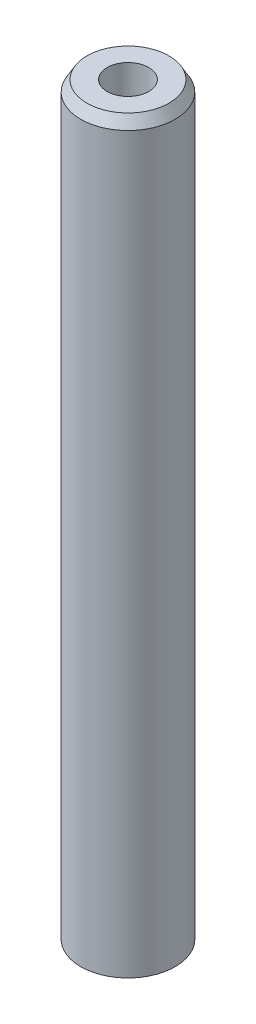
SolidWorks part; units mm, degrees
ref_plane "Front Plane" through (0, 0, 0) normal (0, 0, 1) x (1, 0, 0)
ref_plane "Top Plane" through (0, 0, 0) normal (0, 1, 0) x (1, 0, 0)
ref_plane "Right Plane" through (0, 0, 0) normal (1, 0, 0) x (0, 0, -1)
sketch "Sketch1" plane through (0, 0, 0) normal (0, 1, 0) x (1, 0, 0)
  circle A0 centre (0, 0) radius 20
  dimension "SHAFT_OD" = 40
extrude "Boss-Extrude1" add sketch "Sketch1" along normal blind 317.7219
sketch "Sketch2" plane through (0, 0, 0) normal (0, 1, 0) x (1, 0, 0)
  circle A0 centre (0, 0) radius 8.8079
  dimension "BORE_D" = 17.6158
extrude "Cut-Extrude1" cut sketch "Sketch2" along normal through all
chamfer "Chamfer1" distance 4.574 angle 30 2 edges at (0, 317.7219, 20) (0, 0, 20) first distance on face at (0, 317.7219, 20) first distance on face at (0, 0, 8.8079)
